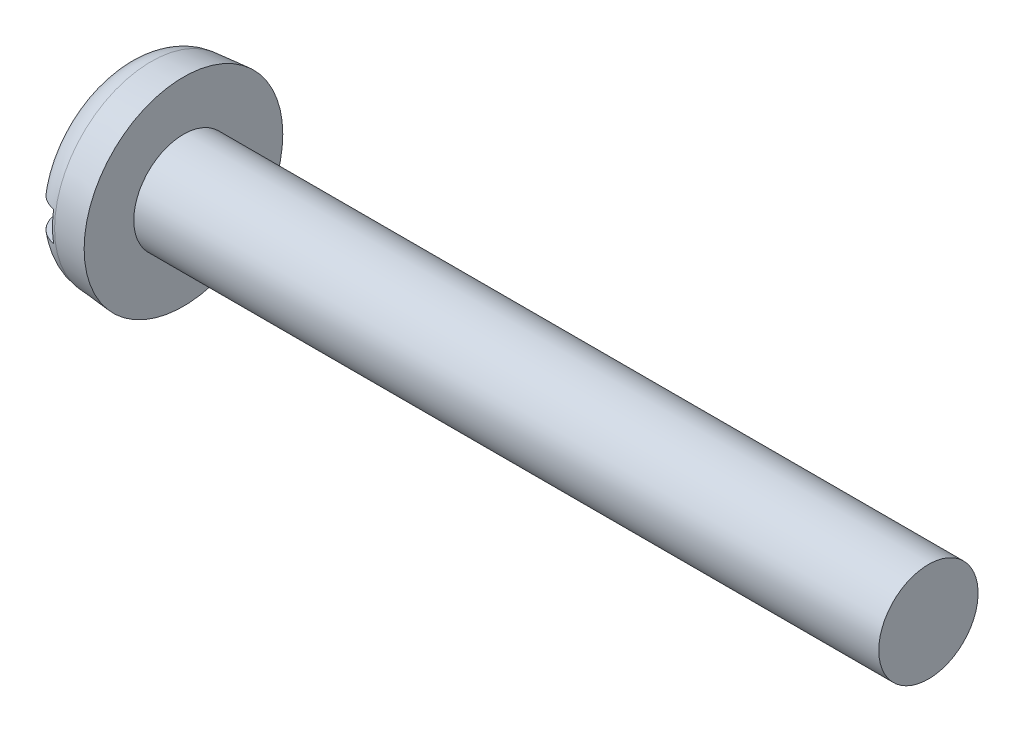
SolidWorks part; units mm, degrees
ref_plane "Plane1" through (0, 0, 0) normal (0, 0, 1) x (1, 0, 0)
ref_plane "Plane2" through (0, 0, 0) normal (0, 1, 0) x (1, 0, 0)
ref_plane "Plane3" through (0, 0, 0) normal (1, 0, 0) x (0, 0, -1)
sketch "BodySke" plane through (0, 0, 0) normal (0, 0, 1) x (1, 0, 0)
  line L0 (2.4, 2) -> (2.4, 4)
  line L1 (0, 0) -> (0, 3.79)
  line L2 (-25.4, 0) -> (127, 0) construction
  line L3 (32.4, 0) -> (0, 0)
  line L4 (2.4, 2) -> (32.4, 2)
  line L5 (32.4, 2) -> (32.4, 0)
  line L6 (0, 3.79) -> (2.4, 4)
  line L9 (3.1, 3.5875) -> (3.1, -5.9375) construction
  line L10 (2.4, 6.35) -> (2.4, -3.175) construction
  dimension "Length" = 30
  dimension "Head_ht" = 2.4
  dimension "Head_dia" = 8
  dimension "Diameter" = 4
revolve "Base-Revolve" add sketch "BodySke"
cosmetic thread "ThreadCosmetic"
fillet "Fillet1" [suppressed] radius 0.2
fillet "Fillet2" radius 1.2 1 edges at (0, 0, 3.79)
sketch "Sketch2" plane through (0, 0, 0) normal (1, 0, 0) x (0, 0, -1)
  line L0 (4, -0.6) -> (-4, -0.6)
  line L1 (4, -0.6) -> (4, 0.6)
  line L2 (-4, 0.6) -> (4, 0.6)
  line L3 (-4, 0.6) -> (-4, -0.6)
  dimension "D1" = 8
  dimension "D2" = 4
  dimension "D3" = 0.6
extrude "Slot" cut sketch "Sketch2" along normal blind 1
sketch "ThdSchSke" plane through (0, 0, 0) normal (0, 0, 1) x (1, 0, 0)
  line L0 (3.8, -1.61) -> (3.5269, -2)
  line L1 (3.8, -1.61) -> (4.0731, -2)
  line L2 (4.0731, -2) -> (4.0731, -2.5)
  line L3 (-3.175, 0) -> (5.1513, 0) construction
  line L5 (4.0731, -2.5) -> (3.5269, -2.5)
  line L6 (3.5269, -2.5) -> (3.5269, -2)
  dimension "Diameter" = 4
  dimension "Thread_minor" = 3.22
  dimension "Start" = 3.8
revolve "ThreadSchematic" [suppressed] cut sketch "ThdSchSke" angle 360 about L3
pattern_linear "ThdSchPat" [suppressed]
ref_axis "Axis1" through (27.6692, 0, 0) along (-1, 0, 0)
equation "\"D1@Sketch2\" = \"Head_dia@BodySke\""
equation "\"D2@Sketch2\" = \"D1@Sketch2\" / 2"
equation "\"D3@Sketch2\" = \"Slot_width@Sketch2\" / 2"
equation "\"Thread_length@ThreadCosmetic\" = ((sgn( (\"Length@BodySke\" - \"Advance@BodySke\" * 2.0 ) - \"Thread_nom@BodySke\" )-1)*( (\"Length@BodySke\" - \"Advance@BodySke\"  * 2.0) - \"Thread_nom@BodySke\" ))/-2+ \"Thread_nom@BodySke\""
equation "\"Thread_minor@ThdSchSke\" = \"Thread_minor@ThreadCosmetic\""
equation "\"Diameter@ThdSchSke\" = \"Diameter@BodySke\""
equation "\"Overcut@ThdSchSke\" = \"Diameter@BodySke\" * 1.25"
equation "\"Start@ThdSchSke\" = \"Head_ht@BodySke\" + \"Length@BodySke\" - \"Thread_length@ThreadCosmetic\"  '---Non-countersunk---"
equation "\"Num_threads@ThdSchPat\" = int( \"Thread_length@ThreadCosmetic\" / \"Advance@BodySke\" + 0.999 )  + 1"
equation "\"Advance@ThdSchPat\" = \"Thread_length@ThreadCosmetic\" /  (\"Num_threads@ThdSchPat\" - 1) 'relax it"
